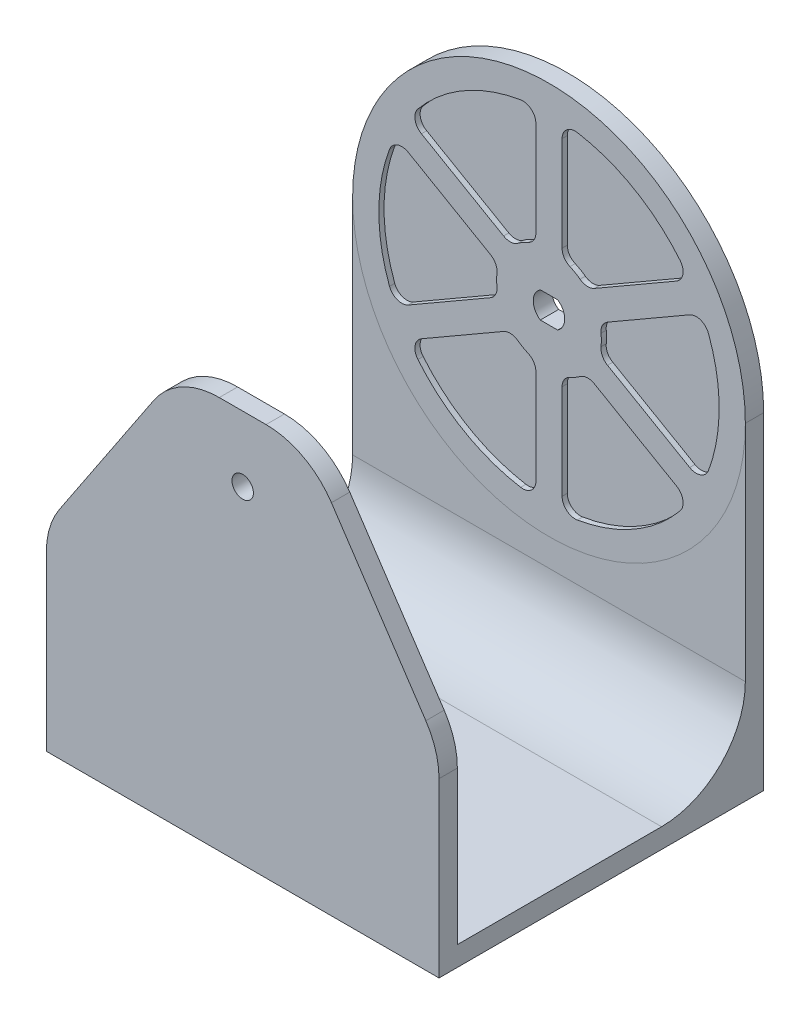
SolidWorks part; units mm, degrees
material "PETG"
ref_plane "Front Plane" through (0, 0, 0) normal (0, 0, 1) x (1, 0, 0)
ref_plane "Top Plane" through (0, 0, 0) normal (0, 1, 0) x (1, 0, 0)
ref_plane "Right Plane" through (0, 0, 0) normal (1, 0, 0) x (0, 0, -1)
sketch "Sketch2" plane through (0, 0, 0) normal (0, 0, 1) x (1, 0, 0)
  line L0 (3.3166, 5) -> (-3.3166, 5)
  line L1 (3.3166, -5) -> (-3.3166, -5)
  circle A0 centre (0, 0) radius 75
  circle A1 centre (0, 0) radius 6
  dimension "D1" = 150
  dimension "D2" = 12
  dimension "D3" = 10
extrude "Boss-Extrude1" add sketch "Sketch2" along normal mid plane 7 contours A0 A1 | L0 A1 | L1 A1 region at (0, 5.403, 0) region at (0, -5.403, 0) region at (-72.8787, 0, 0)
sketch "Sketch7" plane through (0, 0, -3.5) normal (0, 0, -1) x (-1, 0, 0)
  line L0 (-5, 59.1608) -> (-5, 22.9129)
  line L1 (5, 59.1608) -> (5, 22.9129)
  line L2 (-5, 19.3649) -> (5, 19.3649) construction
  line L3 (48.7348, 33.9105) -> (17.3431, 15.7866)
  line L4 (53.7348, 25.2503) -> (22.3431, 7.1263)
  line L6 (53.7348, -25.2503) -> (22.3431, -7.1263)
  line L7 (48.7348, -33.9105) -> (17.3431, -15.7866)
  line L9 (5, -59.1608) -> (5, -22.9129)
  line L10 (-5, -59.1608) -> (-5, -22.9129)
  line L12 (-48.7348, -33.9105) -> (-17.3431, -15.7866)
  line L13 (-53.7348, -25.2503) -> (-22.3431, -7.1263)
  line L15 (-53.7348, 25.2503) -> (-22.3431, 7.1263)
  line L16 (-48.7348, 33.9105) -> (-17.3431, 15.7866)
  line L18 (0, 0) -> (8, 18.3303) construction
  line L19 (14.2705, 14.0126) -> (19.2705, 5.3523) construction
  line L20 (19.2705, -5.3523) -> (14.2705, -14.0126) construction
  line L21 (5, -19.3649) -> (-5, -19.3649) construction
  line L22 (-14.2705, -14.0126) -> (-19.2705, -5.3523) construction
  line L23 (-19.2705, 5.3523) -> (-14.2705, 14.0126) construction
  arc A0 (-8, 18.3303) -> (-11.8745, 16.0934) centre (0, 0) ccw
  arc A1 (-10.8333, 64.0909) -> (-50.0876, 41.4274) centre (0, 0) ccw
  arc A2 (5, 22.9129) -> (8, 18.3303) centre (10, 22.9129) ccw
  arc A3 (5, 59.1608) -> (10.8333, 64.0909) centre (10, 59.1608) cw
  arc A4 (-5, 59.1608) -> (-10.8333, 64.0909) centre (-10, 59.1608) ccw
  arc A5 (-5, 22.9129) -> (-8, 18.3303) centre (-10, 22.9129) cw
  arc A6 (22.3431, 7.1263) -> (19.8745, 2.2369) centre (24.8431, 2.7962) ccw
  arc A7 (53.7348, 25.2503) -> (60.921, 22.6635) centre (56.2348, 20.9201) cw
  arc A8 (48.7348, 33.9105) -> (50.0876, 41.4274) centre (46.2348, 38.2407) ccw
  arc A9 (17.3431, 15.7866) -> (11.8745, 16.0934) centre (14.8431, 20.1167) cw
  arc A10 (17.3431, -15.7866) -> (11.8745, -16.0934) centre (14.8431, -20.1167) ccw
  arc A11 (48.7348, -33.9105) -> (50.0876, -41.4274) centre (46.2348, -38.2407) cw
  arc A12 (53.7348, -25.2503) -> (60.921, -22.6635) centre (56.2348, -20.9201) ccw
  arc A13 (22.3431, -7.1263) -> (19.8745, -2.2369) centre (24.8431, -2.7962) cw
  arc A14 (-5, -22.9129) -> (-8, -18.3303) centre (-10, -22.9129) ccw
  arc A15 (-5, -59.1608) -> (-10.8333, -64.0909) centre (-10, -59.1608) cw
  arc A16 (5, -59.1608) -> (10.8333, -64.0909) centre (10, -59.1608) ccw
  arc A17 (5, -22.9129) -> (8, -18.3303) centre (10, -22.9129) cw
  arc A18 (-22.3431, -7.1263) -> (-19.8745, -2.2369) centre (-24.8431, -2.7962) ccw
  arc A19 (-53.7348, -25.2503) -> (-60.921, -22.6635) centre (-56.2348, -20.9201) cw
  arc A20 (-48.7348, -33.9105) -> (-50.0876, -41.4274) centre (-46.2348, -38.2407) ccw
  arc A21 (-17.3431, -15.7866) -> (-11.8745, -16.0934) centre (-14.8431, -20.1167) cw
  arc A22 (-17.3431, 15.7866) -> (-11.8745, 16.0934) centre (-14.8431, 20.1167) ccw
  arc A23 (-48.7348, 33.9105) -> (-50.0876, 41.4274) centre (-46.2348, 38.2407) cw
  arc A24 (-53.7348, 25.2503) -> (-60.921, 22.6635) centre (-56.2348, 20.9201) ccw
  arc A25 (-22.3431, 7.1263) -> (-19.8745, 2.2369) centre (-24.8431, 2.7962) cw
  arc A26 (11.8745, 16.0934) -> (8, 18.3303) centre (0, 0) ccw
  arc A27 (19.8745, -2.2369) -> (19.8745, 2.2369) centre (0, 0) ccw
  arc A28 (8, -18.3303) -> (11.8745, -16.0934) centre (0, 0) ccw
  arc A29 (-11.8745, -16.0934) -> (-8, -18.3303) centre (0, 0) ccw
  arc A30 (-19.8745, 2.2369) -> (-19.8745, -2.2369) centre (0, 0) ccw
  arc A31 (50.0876, 41.4274) -> (10.8333, 64.0909) centre (0, 0) ccw
  arc A32 (60.921, -22.6635) -> (60.921, 22.6635) centre (0, 0) ccw
  arc A33 (10.8333, -64.0909) -> (50.0876, -41.4274) centre (0, 0) ccw
  arc A34 (-50.0876, -41.4274) -> (-10.8333, -64.0909) centre (0, 0) ccw
  arc A35 (-60.921, 22.6635) -> (-60.921, -22.6635) centre (0, 0) ccw
  point P8 (0, 19.3649)
  dimension "D1" = 130
  dimension "D2" = 40
  dimension "D4" = 5
  dimension "D3" = 10
  dimension "D5" = 6
extrude "Cut-Extrude2" cut sketch "Sketch7" against normal blind 2
mirror "Mirror1" about plane through (0, 0, 0) normal (0, 0, 1) of "Cut-Extrude2"
sketch "Sketch8" plane through (0, 0, 3.5) normal (0, 0, 1) x (1, 0, 0)
  line L0 (-75, 0) -> (-75, -125)
  line L1 (-75, -125) -> (75, -125)
  line L2 (75, -125) -> (75, 0)
  circle A0 centre (0, 0) radius 75 construction
  arc A1 (-75, 0) -> (75, 0) centre (0, 0) ccw
extrude "Boss-Extrude2" add sketch "Sketch8" against normal blind 7 separate body contours A1 L0 L1 | A1 L1 L2 | L2 L1 L0 A1 region at (0, -89.8326, 3.5)
sketch "Sketch11" plane through (0, 0, 3.5) normal (0, 0, 1) x (1, 0, 0)
  line L0 (75, -125) -> (75, 0) construction
  line L1 (-75, -125) -> (75, -125)
  line L2 (-75, -125) -> (-75, -117.4557)
  line L3 (-75, -117.4557) -> (75, -117.4557)
  line L4 (75, -125) -> (75, -117.4557)
extrude "Boss-Extrude4" add sketch "Sketch11" along normal blind 110
sketch "Sketch12" plane through (0, 0, 113.5) normal (0, 0, 1) x (1, 0, 0)
  line L1 (-75, -125) -> (75, -125)
  line L2 (-75, -125) -> (-75, 25.0443)
  line L3 (-75, 25.0443) -> (75, 25.0443)
  line L4 (75, -125) -> (75, 25.0443)
extrude "Boss-Extrude5" add sketch "Sketch12" along normal blind 7
sketch "Sketch13" plane through (0, 0, 120.5) normal (0, 0, 1) x (1, 0, 0)
  line L0 (0, -125) -> (0, 0) construction
  line L1 (-75, -125) -> (75, -125) construction
  circle A0 centre (0, 0) radius 4.1
extrude "Cut-Extrude3" cut sketch "Sketch13" against normal blind 7
fillet "Fillet1" radius 32 1 edges at (0, -117.4557, 3.5)
sketch "Sketch14" plane through (0, 0, 120.5) normal (0, 0, 1) x (1, 0, 0)
  line L0 (-75, -125) -> (-75, -49.9778) construction
  line L1 (-75, 25.0443) -> (-75, -125) construction
  line L2 (0, 25.0443) -> (-25, 25.0443) construction
  line L3 (75, 25.0443) -> (-75, 25.0443) construction
  line L4 (-75, -49.9778) -> (-25, 25.0443)
  line L5 (-25, 25.0443) -> (-75, 25.0443)
  line L6 (-75, 25.0443) -> (-75, -49.9778)
extrude "Cut-Extrude4" cut sketch "Sketch14" against normal blind 7
sketch "Sketch16" plane through (0, 0, 120.5) normal (0, 0, 1) x (1, 0, 0)
  line L0 (75, -125) -> (75, -49.9778) construction
  line L1 (75, -125) -> (75, 25.0443) construction
  line L2 (0, 25.0443) -> (25, 25.0443) construction
  line L3 (75, 25.0443) -> (-25, 25.0443) construction
  line L4 (25, 25.0443) -> (75, -49.9778)
  line L5 (75, -49.9778) -> (75, 25.0443)
  line L6 (25, 25.0443) -> (75, 25.0443)
extrude "Cut-Extrude5" cut sketch "Sketch16" against normal blind 7
fillet "Fillet2" radius 30 1 edges at (-25, 25.0443, 117)
fillet "Fillet3" radius 30 1 edges at (25, 25.0443, 117)
fillet "Fillet4" radius 30 1 edges at (-75, -49.9778, 117)
fillet "Fillet5" radius 30 1 edges at (75, -49.9778, 117)
